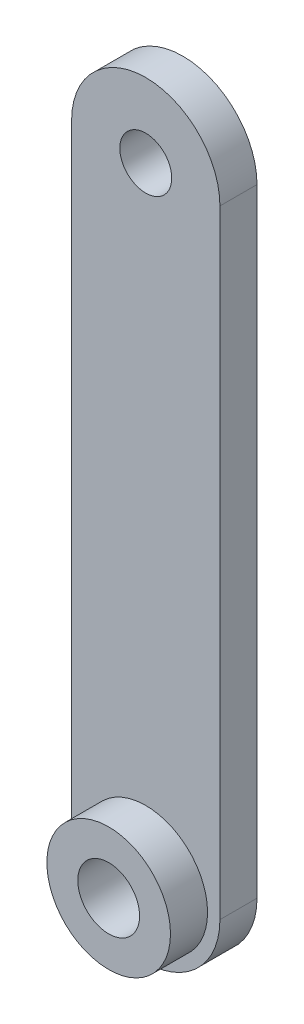
SolidWorks part; units mm, degrees
material "ABS"
ref_plane "Front Plane" through (0, 0, 0) normal (0, 0, 1) x (1, 0, 0)
ref_plane "Top Plane" through (0, 0, 0) normal (0, 1, 0) x (1, 0, 0)
ref_plane "Right Plane" through (0, 0, 0) normal (1, 0, 0) x (0, 0, -1)
sketch "Sketch1" plane through (0, 0, 0) normal (0, 0, 1) x (1, 0, 0)
  line L2 (-6, 50) -> (-6, 0)
  line L3 (6, 50) -> (6, 0)
  arc A3 (6, 50) -> (-6, 50) centre (0, 50) ccw
  arc A4 (-6, 0) -> (6, 0) centre (0, 0) ccw
  point P5 (0, 0)
  point P6 (0, 0)
  point P11 (-0.3811, -21.6883)
  point P26 (-0.3811, 18.3117)
  point P30 (0, 56)
  dimension "D1" = 12
  dimension "D2" = 50
extrude "Boss-Extrude1" add sketch "Sketch1" along normal mid plane 3 contours L3 A3 L2 region at (0, 25, 0)
sketch "Sketch2" plane through (0, 0, 1.5) normal (0, 0, 1) x (1, 0, 0)
  circle A0 centre (0, 0) radius 5
  circle A1 centre (0, 0) radius 2.5
  arc A2 (-6, 0) -> (6, 0) centre (0, 0) ccw construction
  point P5 (0, 0)
  dimension "D1" = 10
  dimension "D2" = 5
extrude "Boss-Extrude2" add sketch "Sketch2" along normal blind 3
extrude "Cut-Extrude1" cut sketch "Sketch2<2>" against normal up to next contours A1 | A1 region at (0, 0, 1.5)
sketch "Sketch2<2>" plane through (0, 0, 1.5) normal (0, 0, 1) x (1, 0, 0) same geometry as "Sketch2"
sketch "Sketch5" plane through (0, 0, 1.5) normal (0, 0, 1) x (1, 0, 0)
  circle A0 centre (0, 50) radius 2.1
  arc A1 (6, 50) -> (-6, 50) centre (0, 50) ccw construction
  dimension "D1" = 4.2
extrude "Cut-Extrude2" cut sketch "Sketch5" against normal up to next contours A0
